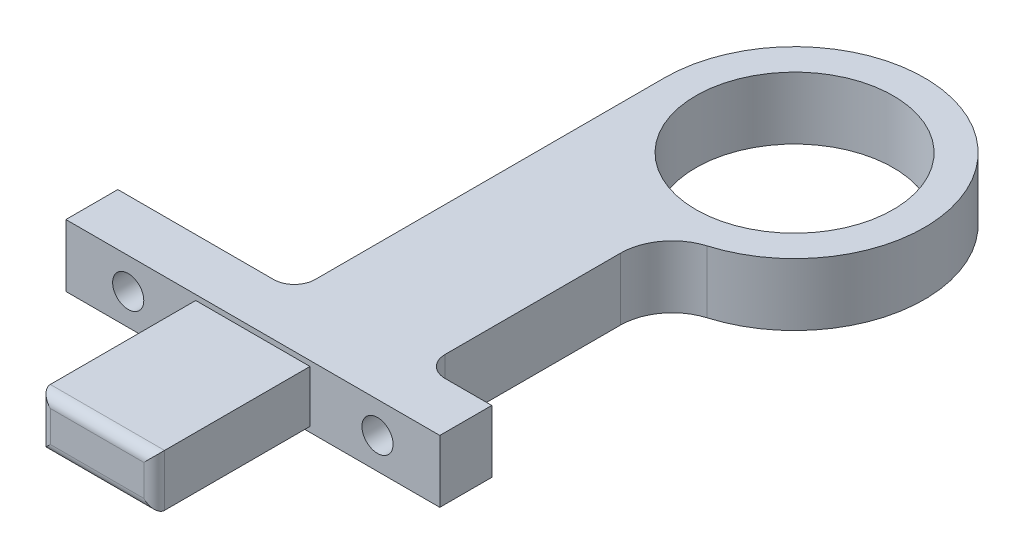
SolidWorks part; units mm, degrees
ref_plane "Alzado" through (0, 0, 0) normal (0, 0, 1) x (1, 0, 0)
ref_plane "Planta" through (0, 0, 0) normal (0, 1, 0) x (1, 0, 0)
ref_plane "Vista lateral" through (0, 0, 0) normal (1, 0, 0) x (0, 0, -1)
sketch "Croquis1" plane through (0, 0, 0) normal (0, 1, 0) x (1, 0, 0)
  line L0 (0, 0) -> (-53.5222, 0) construction
  line L1 (0, 0) -> (-12.5, 21.6506) construction
  line L2 (-25, 21.6506) -> (-25, -12) construction
  line L3 (-24, -34) -> (-24, -19) construction
  line L4 (-30.1777, -19) -> (-17.6777, -19)
  line L5 (-25, -12) -> (-25, 21.6506)
  line L7 (-12.5, -12) -> (-12.5, 4.8801)
  line L8 (-29.5, -19) -> (-18.5, -19)
  line L9 (-29.5, -19) -> (-29.5, -34)
  line L10 (-29.5, -34) -> (-18.5, -34)
  line L11 (-18.5, -19) -> (-18.5, -34)
  line L12 (-42, -14) -> (-27, -14) construction
  line L13 (-10.5, -14) -> (-6, -14) construction
  line L14 (-42, -14) -> (-27, -14)
  line L15 (-42, -14) -> (-42, -19)
  line L16 (-42, -19) -> (-30.1777, -19)
  line L18 (-6, -14) -> (-10.5, -14)
  line L19 (-6, -14) -> (-6, -19)
  line L20 (-6, -19) -> (-17.6777, -19)
  circle A0 centre (0, 0) radius 12.5
  arc A1 (-8.9286, 9.6717) -> (-25, 21.6506) centre (-12.5, 21.6506) ccw
  circle A2 centre (-12.5, 21.6506) radius 9.5
  arc A3 (-10.5, -14) -> (-12.5, -12) centre (-10.5, -12) cw
  arc A4 (-27, -14) -> (-25, -12) centre (-27, -12) ccw
  arc A5 (-8.9286, 9.6717) -> (-12.5, 4.8801) centre (-7.5, 4.8801) ccw
  dimension "D3" = 25
  dimension "D4" = 25
  dimension "D5" = 19
  dimension "D6" = 2
  dimension "D13" = 5
  dimension "D1" = 25
  dimension "D2" = 60
  dimension "D7" = 11
  dimension "D8" = 15
  dimension "D9" = 24
  dimension "D10" = 5
  dimension "D11" = 18
  dimension "D12" = 18
extrude "Saliente-Extruir1" add sketch "Croquis1" along normal blind 6 contours A5 A1 L5 A4 L14 L15 L16 L4 L20 L19 L18 A3 L7 A2 | L11 L4 L9 L10 region at (-18.3892, 0, -1.708) region at (-24, 0, 26.5)
sketch "Croquis2" plane through (0, 0, 19) normal (0, 0, 1) x (1, 0, 0)
  line L0 (-42, 3) -> (-6, 3) construction
  line L1 (-42, 6) -> (-42, 0) construction
  line L2 (-6, 6) -> (-6, 0) construction
  line L3 (-24, 6) -> (-24, 0) construction
  line L4 (-29.5, 6) -> (-18.5, 6) construction
  line L5 (-29.5, 0) -> (-18.5, 0) construction
  circle A0 centre (-36, 3) radius 1.5
  circle A1 centre (-12, 3) radius 1.5
  dimension "D3" = 3
  dimension "D4" = 3
  dimension "D1" = 12
  dimension "D2" = 12
extrude "Cortar-Extruir1" cut sketch "Croquis2" against normal blind 6
sketch "Croquis3" plane through (0, 6, 0) normal (0, 1, 0) x (1, 0, 0)
  line L1 (-18.5, -34) -> (-29.5, -34)
  line L2 (-18.5, -34) -> (-18.5, -19)
  line L3 (-18.5, -19) -> (-29.5, -19)
  line L4 (-29.5, -34) -> (-29.5, -19)
extrude "Cortar-Extruir2" cut sketch "Croquis3" against normal blind 0.5
sketch "Croquis4" plane through (0, 0, 0) normal (0, -1, 0) x (1, 0, 0)
  line L1 (-29.5, 34) -> (-18.5, 34)
  line L2 (-29.5, 34) -> (-29.5, 19)
  line L3 (-29.5, 19) -> (-18.5, 19)
  line L4 (-18.5, 34) -> (-18.5, 19)
extrude "Cortar-Extruir3" cut sketch "Croquis4" against normal blind 0.5
fillet "Redondeo1" radius 1 4 edges at (-29.5, 3, 34) (-24, 5.5, 34) (-18.5, 3, 34) (-24, 0.5, 34)
